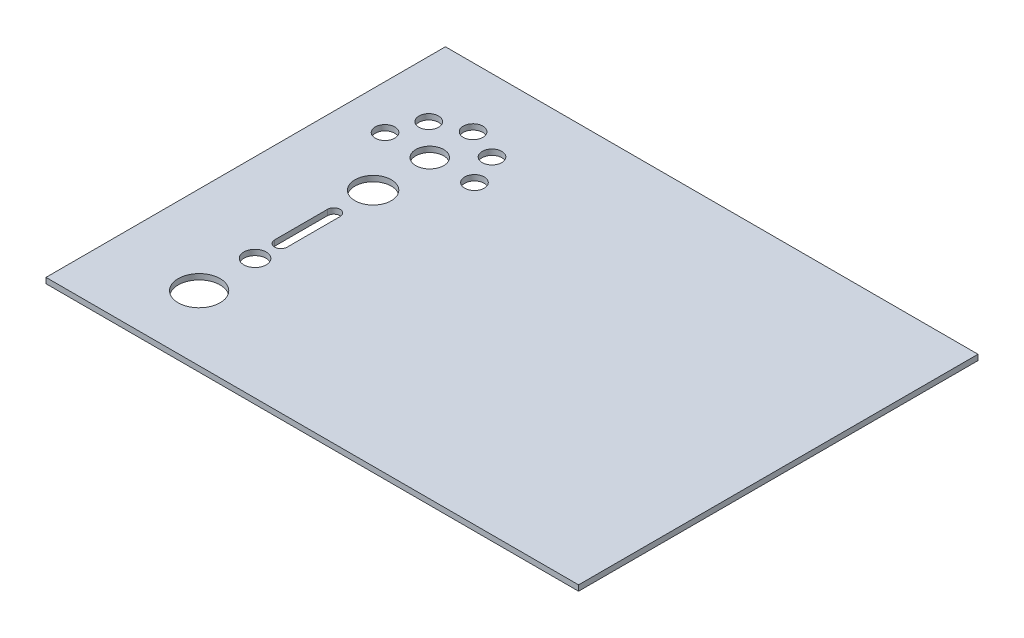
SolidWorks part; units mm, degrees
ref_plane "Front Plane" through (0, 0, 0) normal (0, 0, 1) x (1, 0, 0)
ref_plane "Top Plane" through (0, 0, 0) normal (0, 1, 0) x (1, 0, 0)
ref_plane "Right Plane" through (0, 0, 0) normal (1, 0, 0) x (0, 0, -1)
sketch "Sketch1" plane through (0, 0, 0) normal (0, 1, 0) x (1, 0, 0)
  line L1 (-304.8, 228.6) -> (304.8, 228.6)
  line L2 (-304.8, 228.6) -> (-304.8, -228.6)
  line L3 (-304.8, -228.6) -> (304.8, -228.6)
  line L4 (304.8, 228.6) -> (304.8, -228.6)
  line L5 (-304.8, 228.6) -> (304.8, -228.6) construction
  line L6 (-304.8, -228.6) -> (304.8, 228.6) construction
  point P0 (0, 0)
  dimension "D1" = 609.6
  dimension "D2" = 457.2
extrude "Boss-Extrude1" add sketch "Sketch1" along normal blind 6.35
sketch "Sketch2" plane through (0, 6.35, 0) normal (0, 1, 0) x (1, 0, 0)
  line L0 (-203.9617, 0) -> (-203.9617, -60.5589) construction
  line L1 (-196.7631, 0) -> (-196.7631, -60.5589)
  line L2 (-211.1604, 0) -> (-211.1604, -60.5589)
  circle A0 centre (-203.9617, -154.1413) radius 23.9955
  circle A1 centre (-203.9617, -90.1533) radius 12.7976
  circle A2 centre (-203.9617, 45.0213) radius 20.7961
  circle A3 centre (-203.9617, 109.8092) radius 15.997
  circle A4 centre (-254.3523, 109.0093) radius 11.1979
  circle A5 centre (-240.1588, 144.8751) radius 11.1979
  circle A6 centre (-204.7616, 160.1997) radius 11.1979
  circle A7 centre (-168.8958, 146.0063) radius 11.1979
  circle A8 centre (-153.5712, 110.609) radius 11.1979
  arc A9 (-196.7631, 0) -> (-211.1604, 0) centre (-203.9617, 0) ccw
  arc A10 (-211.1604, -60.5589) -> (-196.7631, -60.5589) centre (-203.9617, -60.5589) ccw
  circle A11 centre (-203.9617, 109.8092) radius 15.997
  circle A12 centre (-203.9617, 109.8092) radius 15.997
  circle A13 centre (-203.9617, 109.8092) radius 15.997
  circle A14 centre (-203.9617, 109.8092) radius 15.997
  point P11 (-203.9617, -30.2794)
  point P20 (-203.9617, 109.8092)
  point P26 (-203.1619, 109.0093)
  point P27 (-254.3523, 109.0093)
  point P28 (-203.9617, 109.8092)
  dimension "D1" = 5
extrude "Cut-Extrude1" cut sketch "Sketch2" against normal through all contours L2 A10 L1 A9 | A2 | A5 | A6 | A7 | A8 | A0 | A1 | A3 | A4 region at (-203.9617, 6.35, 30.2794) region at (-203.9617, 6.35, 154.1413) region at (-203.9617, 6.35, 90.1533) region at (-203.9617, 6.35, -45.0213) region at (-203.9617, 6.35, -109.8092) region at (-254.3523, 6.35, -109.0093) region at (-240.1588, 6.35, -144.8751) region at (-204.7616, 6.35, -160.1997) region at (-168.8958, 6.35, -146.0063) region at (-153.5712, 6.35, -110.609)
